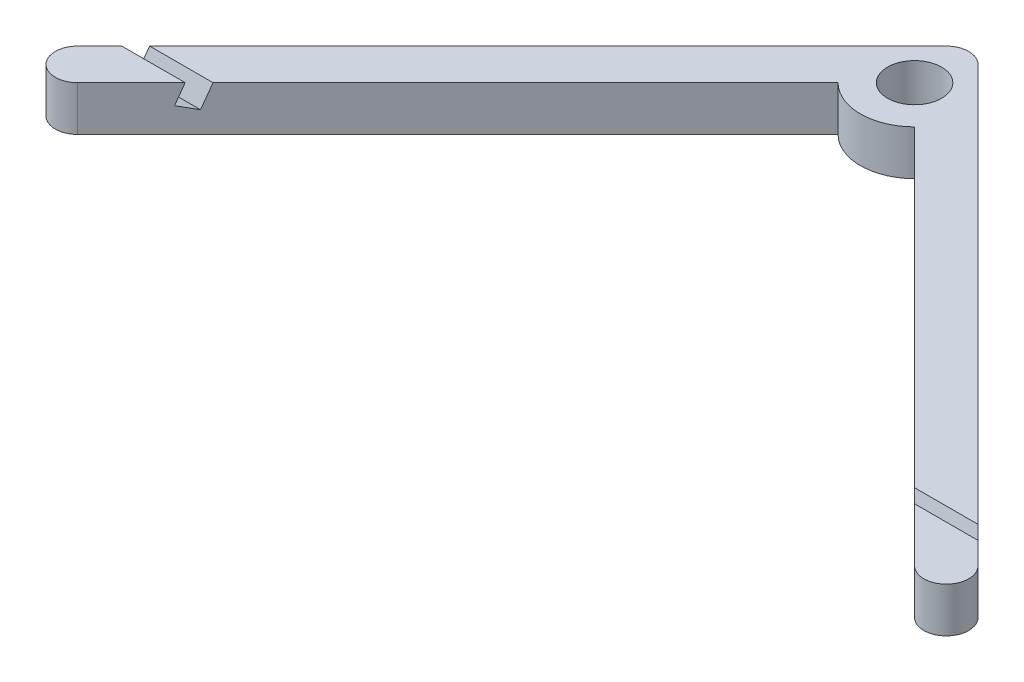
SolidWorks part; units mm, degrees
ref_plane "Front Plane" through (0, 0, 0) normal (0, 0, 1) x (1, 0, 0)
ref_plane "Top Plane" through (0, 0, 0) normal (0, 1, 0) x (1, 0, 0)
ref_plane "Right Plane" through (0, 0, 0) normal (1, 0, 0) x (0, 0, -1)
sketch "Sketch1" plane through (0, 0, 0) normal (0, 1, 0) x (1, 0, 0)
  line L0 (-96.8338, -10) -> (0, 86.8338) construction
  line L1 (-100.3693, -6.4645) -> (-3.5355, 90.3693)
  line L2 (-93.2983, -13.5355) -> (0, 79.7627)
  line L3 (0, 86.8338) -> (96.8338, -10) construction
  line L4 (3.5355, 90.3693) -> (100.3693, -6.4645)
  line L5 (0, 79.7627) -> (93.2983, -13.5355)
  line L6 (-86.8338, 0) -> (86.8338, 0) construction
  line L7 (-3.5355, 83.2983) -> (0, 79.7627) construction
  line L8 (0, 79.7627) -> (3.5355, 83.2983) construction
  line L9 (-100.3693, -6.4645) -> (-93.2983, -13.5355) construction
  line L10 (93.2983, -13.5355) -> (100.3693, -6.4645) construction
  line L11 (0, 86.8338) -> (-3.5355, 90.3693) construction
  line L12 (0, 86.8338) -> (3.5355, 90.3693) construction
  arc A0 (-100.3693, -6.4645) -> (-93.2983, -13.5355) centre (-96.8338, -10) ccw
  arc A1 (3.5355, 90.3693) -> (-3.5355, 90.3693) centre (0, 86.8338) ccw
  arc A2 (3.5355, 90.3693) -> (-3.5355, 90.3693) centre (0, 86.8338) ccw
  arc A3 (93.2983, -13.5355) -> (100.3693, -6.4645) centre (96.8338, -10) ccw
  arc A4 (-3.5355, 90.3693) -> (-3.5355, 83.2983) centre (0, 86.8338) ccw construction
  arc A5 (3.5355, 83.2983) -> (3.5355, 90.3693) centre (0, 86.8338) ccw construction
  point P2 (-16.6441, 6.6441)
  point P7 (16.6441, 6.6441)
  point P8 (96.8338, -10)
  point P22 (0, 0)
  dimension "D1" = 10
  dimension "D2" = 86.8338
  dimension "D3" = 90
  dimension "D4" = 10
extrude "Boss-Extrude1" add sketch "Sketch1" along normal blind 10 contours L5 A3 L4 A1 L1 A0 L2 region at (-50.3262, 0, -40.3262)
sketch "Sketch2" plane through (0, 0, 0) normal (1, 0, 0) x (0, 0, -1)
  line L0 (-2.743, 5.5586) -> (-0.1548, 15.2179)
  line L1 (-2.743, 5.5586) -> (0.1548, 4.7821)
  line L2 (-0.1548, 15.2179) -> (2.743, 14.4414)
  line L3 (0.1548, 4.7821) -> (2.743, 14.4414)
  line L4 (-2.743, 5.5586) -> (2.743, 14.4414) construction
  line L5 (-0.1548, 15.2179) -> (0.1548, 4.7821) construction
  line L6 (90.3693, 10) -> (-6.4645, 10) construction
  line L7 (90.3693, 0) -> (-6.4645, 0) construction
  point P0 (16.0164, 8.8464)
  point P1 (0, 10)
  dimension "D1" = 3
  dimension "D2" = 75
  dimension "D3" = 5
extrude "Cut-Extrude1" cut sketch "Sketch2" against normal through all both and the other way through all
sketch "Sketch3" plane through (0, 0, 0) normal (0, 1, 0) x (1, 0, 0)
  line L0 (-78.2098, 1.5529) -> (0, 79.7627) construction
  line L1 (0, 79.7627) -> (78.2098, 1.5529) construction
  line L2 (0, 91.8338) -> (0, 67.6917) construction
  line L3 (0, 79.7627) -> (8.5355, 71.2272)
  line L4 (-8.5355, 71.2272) -> (0, 79.7627)
  line L5 (-78.2098, 1.5529) -> (-8.5355, 71.2272) construction
  line L6 (8.5355, 71.2272) -> (78.2098, 1.5529) construction
  arc A0 (-8.5355, 71.2272) -> (8.5355, 71.2272) centre (0, 79.7627) ccw
  arc A1 (3.5355, 90.3693) -> (-3.5355, 90.3693) centre (0, 86.8338) ccw construction
  point P13 (0, 79.7627)
extrude "Boss-Extrude2" add sketch "Sketch3" along normal up to surface (10 mm away) up to face at (0, 10, -38.3111)
sketch "Sketch4" plane through (0, 0, 0) normal (0, 1, 0) x (1, 0, 0)
  line L0 (0, 91.8338) -> (0, 85.7983) construction
  line L1 (0, 85.7983) -> (0, 73.7272) construction
  line L2 (0, 73.7272) -> (0, 67.6917) construction
  line L3 (12.0711, 79.7627) -> (12.0711, 67.6917) construction
  line L4 (12.0711, 67.6917) -> (0, 67.6917) construction
  circle A0 centre (0, 79.7627) radius 12.0711
  circle A1 centre (0, 79.7627) radius 6.0355
  arc A2 (-8.5355, 71.2272) -> (8.5355, 71.2272) centre (0, 79.7627) ccw construction
  point P13 (0, 0)
extrude "Cut-Extrude2" cut sketch "Sketch4" along normal through all contours A1 region at (0, 0, -79.7627)
equation "\"BoardReclineAngle\"= 75"
equation "\"BoardHeight\"= 305"
equation "\"BoardWidth\"= 244"
equation "\"LegDivergingAngle\"= 90"
equation "\"FrontProtrusion\"=10"
equation "\"D4@Sketch1\"=\"FrontProtrusion\""
equation "\"D2@Sketch1\"=(\"BoardHeight\"*cos( \"BoardReclineAngle\"))*\"SafetyFactor\""
equation "\"HolderSlotThickness\"=3"
equation "\"D1@Sketch2\"=\"HolderSlotThickness\""
equation "\"SafetyFactor\"= 1.1"
